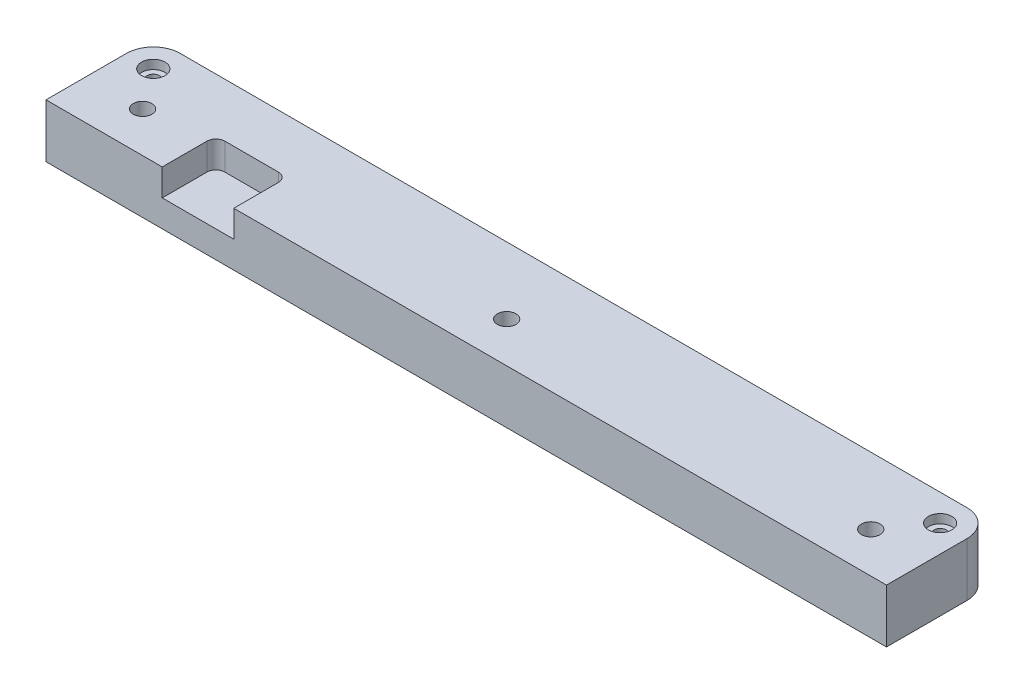
SolidWorks part; units mm, degrees
ref_plane "Front Plane" through (0, 0, 0) normal (0, 0, 1) x (1, 0, 0)
ref_plane "Top Plane" through (0, 0, 0) normal (0, 1, 0) x (1, 0, 0)
ref_plane "Right Plane" through (0, 0, 0) normal (1, 0, 0) x (0, 0, -1)
sketch "Sketch1" plane through (0, 0, 0) normal (0, 1, 0) x (1, 0, 0)
  line L1 (0, 0) -> (298.45, 0)
  line L2 (0, 0) -> (0, 38.1)
  line L3 (0, 38.1) -> (298.45, 38.1)
  line L4 (298.45, 0) -> (298.45, 38.1)
  dimension "D1" = 38.1
  dimension "D2" = 298.45
extrude "Boss-Extrude1" add sketch "Sketch1" along normal blind 19.05
fillet "Fillet1" radius 9.525 2 edges at (298.45, 9.525, -38.1) (0, 9.525, -38.1)
sketch "Sketch2" plane through (0, 19.05, 0) normal (0, 1, 0) x (1, 0, 0)
  line L0 (0, 14.351) -> (298.45, 14.351) construction
  line L1 (0, 28.575) -> (0, 0) construction
  line L2 (298.45, 0) -> (298.45, 28.575) construction
  line L3 (288.925, 38.1) -> (9.525, 38.1) construction
  circle A0 centre (19.939, 14.351) radius 3.302
  circle A1 centre (149.225, 14.351) radius 3.302
  circle A2 centre (278.511, 14.351) radius 3.302
  dimension "D2" = 6.604
  dimension "D1" = 23.749
  dimension "D3" = 19.939
  dimension "D4" = 19.939
extrude "Cut-Extrude1" cut sketch "Sketch2" against normal blind 14.2875
sketch "Sketch4" plane through (0, 0, 0) normal (0, -1, 0) x (1, 0, 0)
  circle A0 centre (19.939, -14.351) radius 1.6256
  circle A1 centre (149.225, -14.351) radius 1.6256
  circle A2 centre (278.511, -14.351) radius 1.6256
  dimension "D1" = 3.2512
extrude "Cut-Extrude2" cut sketch "Sketch4" against normal through all
sketch "Sketch5" plane through (0, 0, 0) normal (0, -1, 0) x (1, 0, 0)
  circle A0 centre (19.939, -14.351) radius 2.667
  circle A1 centre (149.225, -14.351) radius 2.667
  circle A2 centre (278.511, -14.351) radius 2.667
  dimension "D1" = 5.334
extrude "Cut-Extrude3" cut sketch "Sketch5" against normal blind 2.921
sketch "Sketch6" plane through (0, 19.05, 0) normal (0, 1, 0) x (1, 0, 0)
  line L0 (298.45, 28.575) -> (0, 28.575) construction
  line L1 (0, 28.575) -> (0, 0) construction
  line L2 (298.45, 0) -> (298.45, 28.575) construction
  circle A0 centre (9.525, 28.575) radius 2.1844
  circle A1 centre (288.925, 28.575) radius 2.1844
  dimension "D3" = 4.3688
  dimension "D1" = 9.525
  dimension "D2" = 9.525
extrude "Cut-Extrude4" cut sketch "Sketch6" against normal through all contours L0 A1 | A1 L0 | A0 region at (288.925, 19.05, -27.6479) region at (288.925, 19.05, -29.5021)
sketch "Sketch7" plane through (0, 19.05, 0) normal (0, 1, 0) x (1, 0, 0)
  line L0 (288.925, 38.1) -> (9.525, 38.1) construction
  line L1 (149.225, 28.575) -> (149.225, 38.1) construction
  line L2 (140.3895, 28.575) -> (144.8073, 20.9233)
  line L3 (144.8073, 20.9233) -> (153.6427, 20.9233)
  line L4 (153.6427, 20.9233) -> (158.0605, 28.575)
  line L5 (158.0605, 28.575) -> (153.6427, 36.2268)
  line L6 (153.6427, 36.2268) -> (144.8073, 36.2268)
  line L7 (144.8073, 36.2268) -> (140.3895, 28.575)
  line L8 (288.925, 38.1) -> (9.525, 38.1) construction
  circle A1 centre (149.225, 28.575) radius 7.6517 construction
  dimension "D1" = 9.525
  dimension "D3" = 15.3035
extrude "Cut-Extrude5" cut sketch "Sketch7" against normal through all from offset 6.35 offset against normal yes
sketch "Sketch8" plane through (0, 0, 0) normal (0, -1, 0) x (1, 0, 0)
  line L0 (0, 0) -> (298.45, 0) construction
  line L1 (41.275, 0) -> (66.675, 0)
  line L2 (41.275, 0) -> (41.275, -19.05)
  line L3 (41.275, -19.05) -> (66.675, -19.05)
  line L4 (66.675, 0) -> (66.675, -19.05)
  line L5 (0, -28.575) -> (0, 0) construction
  dimension "D1" = 41.275
  dimension "D2" = 25.4
  dimension "D3" = 19.05
extrude "Cut-Extrude6" cut sketch "Sketch8" against normal blind 9.525 from offset 9.525 offset against normal yes
fillet "Fillet2" radius 3.175 2 edges at (66.675, 14.2875, -19.05) (41.275, 14.2875, -19.05)
fillet "Fillet3" radius 1.5875 6 edges at (144.8073, 6.35, -36.2268) (140.3895, 6.35, -28.575) (144.8073, 6.35, -20.9233) (153.6427, 6.35, -20.9233) (158.0605, 6.35, -28.575) (153.6427, 6.35, -36.2268)
sketch "Sketch11" plane through (0, 19.05, 0) normal (0, 1, 0) x (1, 0, 0)
  circle A0 centre (9.525, 28.575) radius 4.1669
  circle A1 centre (288.925, 28.575) radius 4.1669
  dimension "D1" = 8.3337
extrude "Cut-Extrude7" cut sketch "Sketch11" against normal blind 3.175
